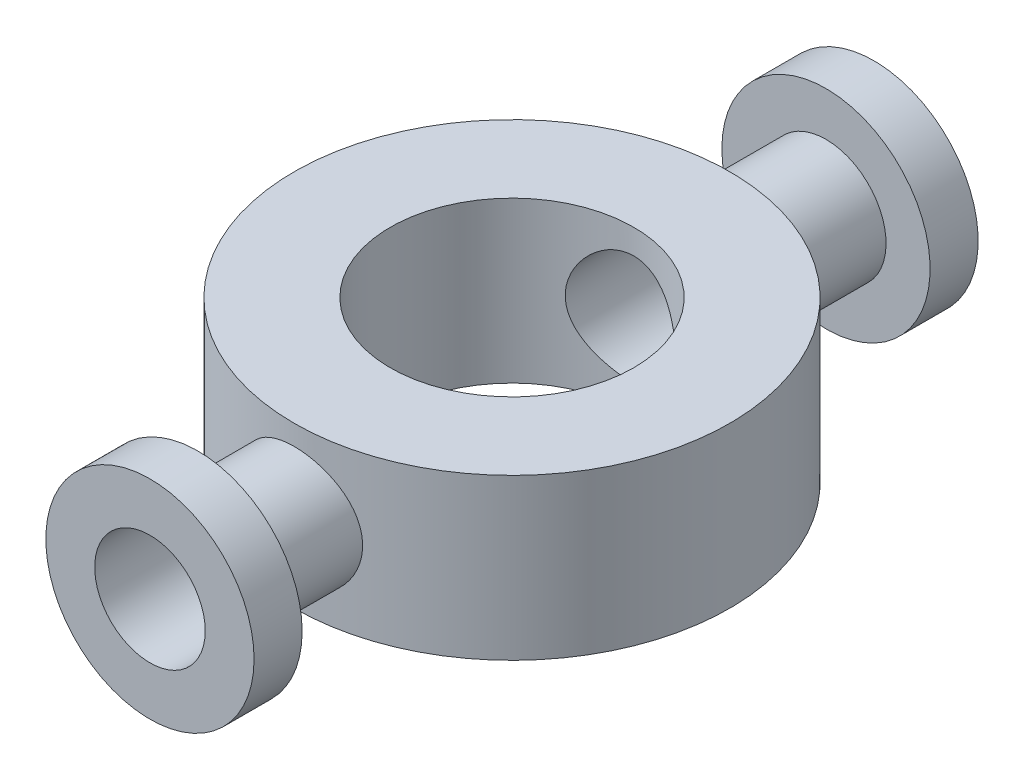
SolidWorks part; units mm, degrees
ref_plane "Front Plane" through (0, 0, 0) normal (0, 0, 1) x (1, 0, 0)
ref_plane "Top Plane" through (0, 0, 0) normal (0, 1, 0) x (1, 0, 0)
ref_plane "Right Plane" through (0, 0, 0) normal (1, 0, 0) x (0, 0, -1)
sketch "Sketch1" plane through (0, 0, 0) normal (0, 1, 0) x (1, 0, 0)
  circle A0 centre (0, 0) radius 34.544
  dimension "D1" = 69.088
extrude "Extrude-Thin1" add sketch "Sketch1" along normal mid plane 25.4 thin thin type one direction reverse wall 15.24
ref_plane "Plane1" through (0, 0, 34.544) normal (0, 0, 1) x (1, 0, 0)
ref_plane "Plane2" through (0, 0, -34.544) normal (0, 0, -1) x (-1, 0, 0)
sketch "Sketch2" plane through (0, 0, 0) normal (0, 0, 1) x (1, 0, 0)
  circle A0 centre (0, 0) radius 8.763
  dimension "D1" = 17.526
extrude "Cut-Extrude1" cut sketch "Sketch2" against normal through all both and the other way through all
extrude "Extrude-Thin2" add sketch "Sketch2<3>" along normal blind 22.86 and the other way up to surface from surface thin other way up to face at (1.7052, -8.5955, -34.5019) starting at plane "Plane1" thin type one direction wall 0.762
sketch "Sketch2<3>" plane through (0, 0, 0) normal (0, 0, 1) x (1, 0, 0) same geometry as "Sketch2"
extrude "Extrude-Thin4" add sketch "Sketch2<5>" against normal blind 22.86 and the other way up to surface from surface thin other way up to face at (0, -12.7, 34.544) starting at plane "Plane2" thin type one direction wall 0.762
sketch "Sketch2<5>" plane through (0, 0, 0) normal (0, 0, 1) x (1, 0, 0) same geometry as "Sketch2"
extrude "Extrude-Thin3" add sketch "Sketch2<4>" against normal blind 7.62 from surface thin starting at face at (9.525, 0, 57.404) thin type one direction wall 7.747
sketch "Sketch2<4>" plane through (0, 0, 0) normal (0, 0, 1) x (1, 0, 0) same geometry as "Sketch2"
extrude "Extrude-Thin5" add sketch "Sketch2<6>" along normal blind 7.62 from surface thin starting at face at (-9.525, 0, -57.404) thin type one direction wall 7.747
sketch "Sketch2<6>" plane through (0, 0, 0) normal (0, 0, 1) x (1, 0, 0) same geometry as "Sketch2"
